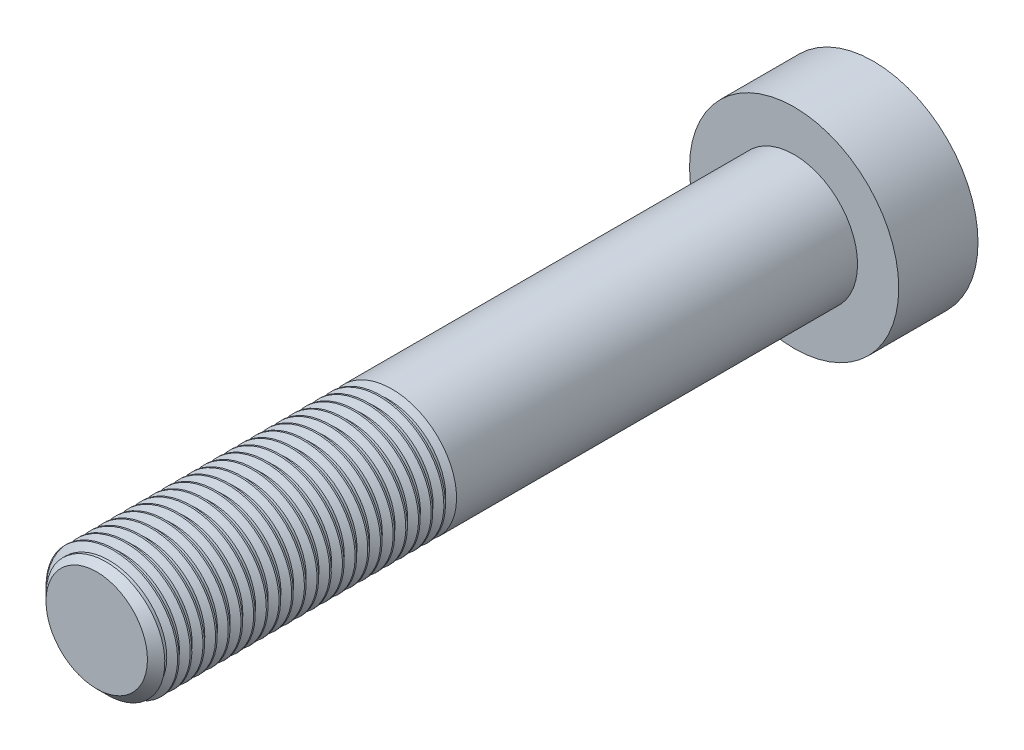
SolidWorks part; units mm, degrees
ref_plane "Спереди" through (0, 0, 0) normal (0, 0, 1) x (1, 0, 0)
ref_plane "Сверху" through (0, 0, 0) normal (0, 1, 0) x (1, 0, 0)
ref_plane "Справа" through (0, 0, 0) normal (1, 0, 0) x (0, 0, -1)
sketch "Эскиз1" plane through (0, 0, 0) normal (0, 0, 1) x (1, 0, 0)
  circle A0 centre (0, 0) radius 10
  dimension "D1" = 20
extrude "Бобышка-Вытянуть1" add sketch "Эскиз1" along normal blind 110
sketch "Эскиз2" plane through (0, 0, 0) normal (0, 0, -1) x (-1, 0, 0)
  circle A0 centre (0, 0) radius 16.5
  dimension "D1" = 33
extrude "Бобышка-Вытянуть2" add sketch "Эскиз2" along normal blind 12.5
chamfer "Фаска1" distance 2 angle 45 1 edges at (10, 0, 110)
thread "Резьба1" pitch 2 method cut profile "Профиль резьбы1" start angle 0, offset 0, length 46, pitch 2, diameter 20
ref_plane "Плоскость1" through (-10, 0, 110) normal (0, -1, 0) x (-1, 0, 0)
sketch "Профиль резьбы1" plane through (-10, 0, 110) normal (0, -1, 0) x (-1, 0, 0)
  line L0 (0, 0) -> (0, 2) construction
  line L11 (0, 0) -> (0, 1.75)
  line L12 (0, 1.75) -> (-1.0825, 1.125)
  line L13 (-1.0825, 1.125) -> (-1.0825, 0.625)
  line L15 (-1.0825, 0.625) -> (0, 0)
  line L17 (-1.0825, 0.875) -> (0, 0.875) construction
  point P2 (0, 0)
  dimension "Pitch" = 2
  dimension "Profile_Angle" = 60
  dimension "Profile_Land" = 0.5
  dimension "Profile_Height" = 1.0825
